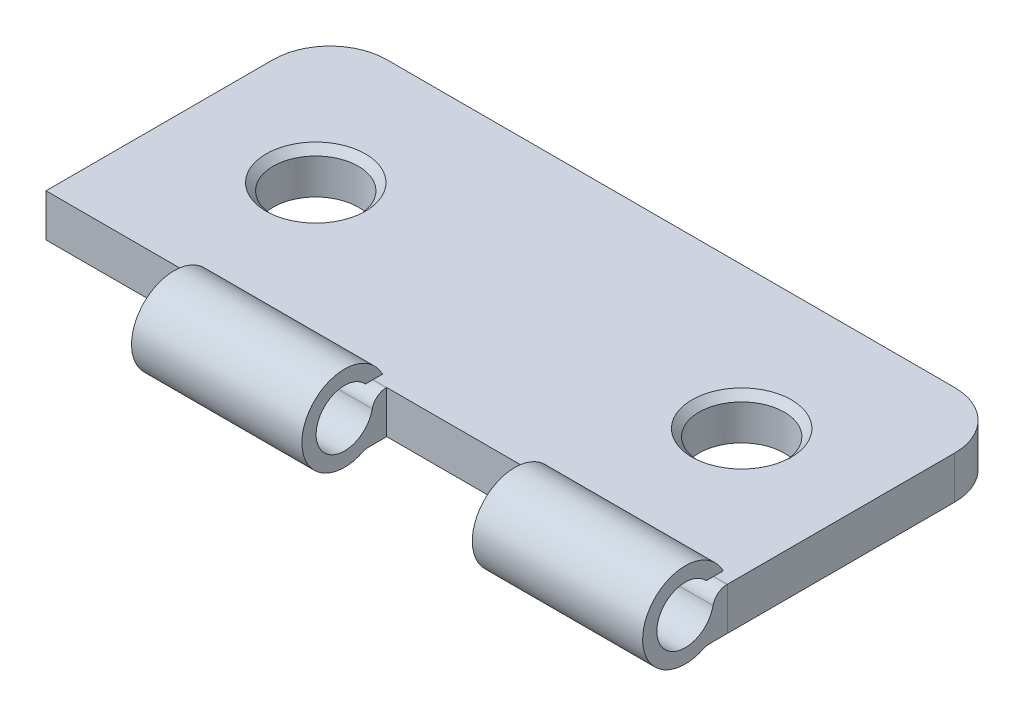
SolidWorks part; units mm, degrees
ref_plane "Front Plane" through (0, 0, 0) normal (0, 0, 1) x (1, 0, 0)
ref_plane "Top Plane" through (0, 0, 0) normal (0, 1, 0) x (1, 0, 0)
ref_plane "Right Plane" through (0, 0, 0) normal (1, 0, 0) x (0, 0, -1)
sketch "Sketch1" plane through (0, 0, 0) normal (0, 1, 0) x (1, 0, 0)
  line L1 (-12, -5) -> (12, -5)
  line L2 (-12, -5) -> (-12, 3)
  line L3 (-10, 5) -> (10, 5)
  line L4 (12, -5) -> (12, 3)
  line L5 (-12, -5) -> (12, 5) construction
  line L6 (-12, 5) -> (12, -5) construction
  circle A0 centre (-7.5, 0) radius 1.5
  circle A1 centre (7.5, 0) radius 1.5
  arc A2 (10, 5) -> (12, 3) centre (10, 3) cw
  arc A3 (-12, 3) -> (-10, 5) centre (-10, 3) cw
  point P0 (0, 0)
  dimension "D1" = 15
  dimension "D2" = 3
  dimension "D3" = 3
  dimension "D4" = 7.5
  dimension "D5" = 10
  dimension "D7" = 2
  dimension "D6" = 24
extrude "Boss-Extrude1" add sketch "Sketch1" along normal blind 1.5
sketch "Sketch2" plane through (12, 0, 0) normal (1, 0, 0) x (0, 0, -1)
  line L0 (-5.7489, 1.9805) -> (-5.1475, 1.9805)
  line L1 (-5, 0) -> (-5.6288, 0)
  line L2 (-5, 0) -> (-5, 1.5)
  line L3 (-5, 1.5) -> (-5.019, 1.5)
  arc A0 (-5.1475, 1.9805) -> (-5.8434, -0.0484) centre (-6.4874, 1.3063) ccw
  arc A1 (-5.7489, 1.9805) -> (-5.5085, 1.1021) centre (-6.4874, 1.3063) ccw
  arc A2 (-5, 1.1126) -> (-5, 1.5) centre (-6.4874, 1.3063) ccw
  arc A3 (-5.6288, 0) -> (-5.8434, -0.0484) centre (-5.6288, -0.5) ccw
  arc A4 (-5.019, 1.5) -> (-5.5085, 1.1021) centre (-5.019, 1) ccw
  line M12 (-5, 1.5) -> (-5, 0)
  dimension "D1" = 3
  dimension "D2" = 2
  dimension "D3" = 0.5
extrude "Boss-Extrude2" add sketch "Sketch2" against normal blind 6 separate body contours L3 A4 A1 L0 A0 A3 L1 L2 M12 region at (12, 1.0312, 7.4928)
pattern_linear "LPattern1" count 2 spacing 12 along (-1, 0, 0) of "Boss-Extrude2"
chamfer "Chamfer1" distance 0.25 angle 45 2 edges at (7.5, 1.5, 1.5) (-7.5, 1.5, 1.5)
